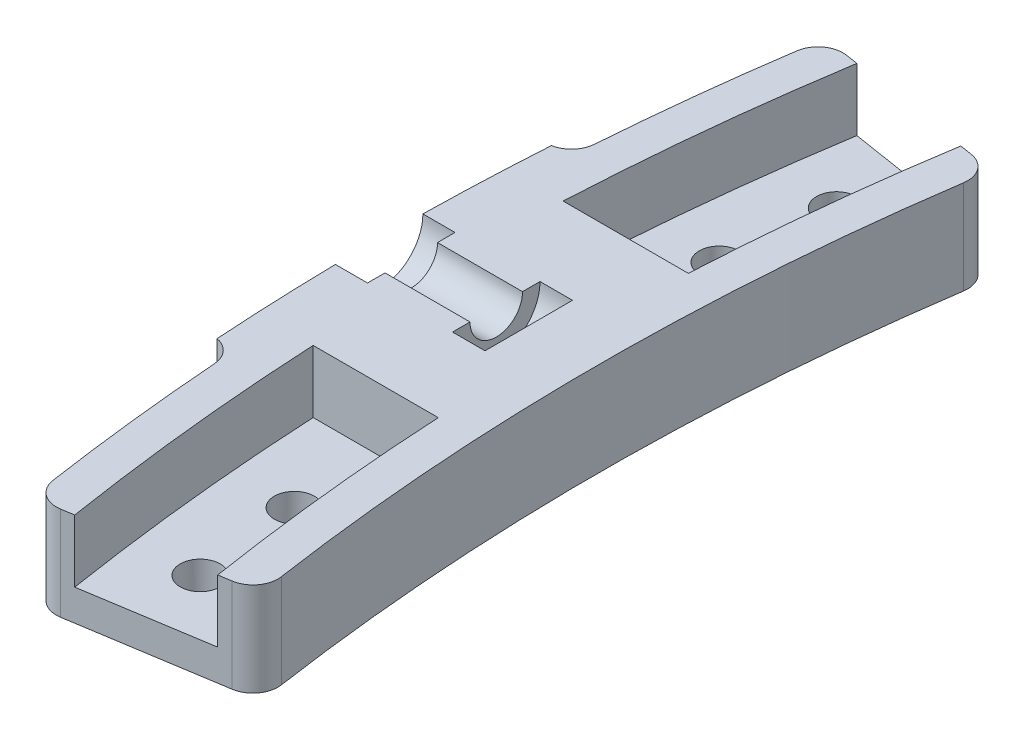
SolidWorks part; units mm, degrees
ref_plane "Front Plane" through (0, 0, 0) normal (0, 0, 1) x (1, 0, 0)
ref_plane "Top Plane" through (0, 0, 0) normal (0, 1, 0) x (1, 0, 0)
ref_plane "Right Plane" through (0, 0, 0) normal (1, 0, 0) x (0, 0, -1)
sketch "Sketch1" plane through (0, 0, 0) normal (0, 1, 0) x (1, 0, 0)
  line L0 (0, 0) -> (-197.5377, -31.2869) construction
  line L1 (0, 0) -> (-197.5377, 31.2869) construction
  line L2 (0, 0) -> (-195, 0) construction
  line L3 (-197.5377, 31.2869) -> (-187.6608, 29.7225)
  line L4 (-187.6608, -29.7225) -> (-197.5377, -31.2869)
  line L5 (0, 0) -> (-200.5007, -31.7562) construction
  line L6 (0, 0) -> (-200.5007, 31.7562) construction
  line L7 (-200.5007, 31.7562) -> (-184.6977, 29.2532)
  line L8 (-200.5007, -31.7562) -> (-184.6977, -29.2532)
  arc A0 (-197.5377, 31.2869) -> (-197.5377, -31.2869) centre (0, 0) ccw
  arc A1 (-187.6608, 29.7225) -> (-187.6608, -29.7225) centre (0, 0) ccw
  arc A2 (-192.5992, -30.5047) -> (-192.5992, 30.5047) centre (0, 0) cw construction
  arc A4 (-184.6977, 29.2532) -> (-184.6977, -29.2532) centre (0, 0) ccw
  arc A5 (-200.5007, 31.7562) -> (-200.5007, -31.7562) centre (0, 0) ccw
  dimension "D1" = 200
  dimension "D2" = 190
  dimension "D3" = 5
  dimension "D5" = 187
  dimension "D6" = 203
  dimension "D4" = 18
extrude "Boss-Extrude1" add sketch "Sketch1" along normal blind 7.5 contours A1 L3 A0 L4 | L7 A5 L8 A0 | A4 L7 A1 L8 region at (-200.6761, 0, 0) region at (-194.2416, 0, 0) region at (-187.7297, 0, 0)
ref_plane "Plane1" through (-195, 0, 0) normal (1, 0, 0) x (0, 0, -1)
sketch "Sketch19" plane through (0, 0, 0) normal (0, 1, 0) x (1, 0, 0)
  line L0 (0, 0) -> (-204.0621, 13.3749) construction
  line L1 (0, 0) -> (-204.0621, -13.3749) construction
  line L4 (0, 0) -> (-204.5, 0) construction
  line L5 (-204.0621, 13.3749) -> (-202.5654, 13.2768)
  line L6 (-204.0621, -13.3749) -> (-202.5654, -13.2768)
  arc A0 (-204.0621, 13.3749) -> (-204.0621, -13.3749) centre (0, 0) ccw
  arc A1 (-200.5007, 31.7562) -> (-200.5007, -31.7562) centre (0, 0) ccw construction
  arc A2 (-202.5654, 13.2768) -> (-202.5654, -13.2768) centre (0, 0) ccw
  dimension "D1" = 204.5
  dimension "D2" = 3.75
extrude "Boss-Extrude2" add sketch "Sketch19" along normal blind 7.5
sketch "Sketch15" plane through (0, 7.5, 0) normal (0, 1, 0) x (1, 0, 0)
  line L0 (-187.6608, -29.7225) -> (-197.5377, -31.2869) construction
  line L1 (-185, 10) -> (-205, 10)
  line L2 (-185, 10) -> (-185, -10)
  line L3 (-185, -10) -> (-205, -10)
  line L4 (-205, 10) -> (-205, -10)
  line L5 (-185, 10) -> (-205, -10) construction
  line L6 (-185, -10) -> (-205, 10) construction
  line L7 (-197.5377, 31.2869) -> (-187.6608, 29.7225) construction
  line L8 (-187.6608, -29.7225) -> (-197.5377, -31.2869)
  line L9 (-197.5377, 31.2869) -> (-187.6608, 29.7225)
  arc A2 (-187.6608, 29.7225) -> (-187.6608, -29.7225) centre (0, 0) ccw construction
  arc A3 (-197.5377, 31.2869) -> (-197.5377, -31.2869) centre (0, 0) ccw construction
  arc A4 (-187.6608, 29.7225) -> (-187.6608, -29.7225) centre (0, 0) ccw
  arc A5 (-197.5377, 31.2869) -> (-197.5377, -31.2869) centre (0, 0) ccw
  point P0 (-195, 0)
  line M5 (-200.5007, -31.7562) -> (-184.6977, -29.2532)
  line M7 (-184.6977, 29.2532) -> (-200.5007, 31.7562)
  dimension "D1" = 20
  dimension "D2" = 20
extrude "Cut-Extrude1" cut sketch "Sketch15" against normal blind 5 contours A5 L1 A4 M7 | L3 A5 A4 M5 region at (-193.9153, 7.5, -20.2762) region at (-193.9153, 7.5, 20.2762)
ref_plane "Plane2" through (-195, 0, 0) normal (-1, 0, 0) x (0, 0, 1)
sketch "Sketch12" plane through (0, 0, 0) normal (0, 1, 0) x (1, 0, 0)
  line L0 (0, 0) -> (-194.258, -16.9954) construction
  line L1 (0, 0) -> (-193.3317, -25.4526) construction
  line L2 (0, 0) -> (-195, 0) construction
  line L3 (0, 0) -> (-195, 0) construction
  line L4 (0, 0) -> (-194.258, 16.9954) construction
  line L5 (0, 0) -> (-193.3317, 25.4526) construction
  arc A0 (-192.5992, 30.5047) -> (-192.5992, -30.5047) centre (0, 0) ccw construction
  dimension "D1" = 10
  dimension "D2" = 15
hole_wizard "Ø3.2 (3.2) Diameter Hole1" positions "Sketch18" profile "Sketch17" hole size "Ø3.2" standard "ISO" end condition through all
sketch "Sketch18" plane through (0, 0, 0) normal (0, -1, 0) x (-1, 0, 0)
  point P0 (193.3317, -25.4526)
  point P3 (194.258, -16.9954)
  point P6 (194.258, 16.9954)
  point P9 (193.3317, 25.4526)
sketch "Sketch17" plane through (-193.3317, 0, 25.4526) normal (1, 0, 0) x (0, 0, -1)
  line L0 (0, 0) -> (0, 7.5)
  line L1 (0, 7.5) -> (1.6, 7.5)
  line L2 (1.6, 7.5) -> (1.6, 0)
  line L5 (1.6, 0) -> (0, 0)
  line L11 (0, -6.35) -> (0, 107.95) construction
  dimension "Thru Hole Dia." = 3.2
  dimension "Thru Hole Depth" = 7.5
sketch "Sketch20" plane through (0, 0, 0) normal (0, 1, 0) x (1, 0, 0)
  line L0 (-205, 0) -> (-192.5, 0) construction
  line L1 (0, 0) -> (-205, 0) construction
  arc A2 (-204.0621, 13.3749) -> (-204.0621, -13.3749) centre (0, 0) ccw construction
  point P3 (-204.5, 0)
  dimension "D1" = 205
  dimension "D2" = 12.5
ref_plane "Plane3" through (-192.5, 0, 0) normal (1, 0, 0) x (0, 0, -1)
sketch "Sketch21" plane through (-192.5, 0, 0) normal (1, 0, 0) x (0, 0, -1)
  line L0 (29.2532, 7.5) -> (-29.2532, 7.5) construction
  circle A0 centre (0, 7.5) radius 3.5
  dimension "D1" = 7
extrude "Cut-Extrude2" cut sketch "Sketch21" against normal blind 2.6
sketch "Sketch22" plane through (-195.1, 0, 0) normal (1, 0, 0) x (0, 0, -1)
  line L0 (29.2532, 7.5) -> (-29.2532, 7.5) construction
  circle A0 centre (0, 7.5) radius 2.1
  dimension "D1" = 4.2
ref_plane "Plane4" through (-204.5, 0, 0) normal (1, 0, 0) x (0, 0, -1)
sketch "Sketch23" plane through (-204.5, 0, 0) normal (1, 0, 0) x (0, 0, -1)
  circle A0 centre (0, 7.5) radius 3.5
  dimension "D1" = 7
extrude "Cut-Extrude3" cut sketch "Sketch23" along normal blind 2.6
extrude "Cut-Extrude4" cut sketch "Sketch22" against normal through all contours A0
fillet "Fillet1" radius 2 4 edges at (-200.5007, 3.75, -31.7562) (-184.6977, 3.75, -29.2532) (-184.6977, 3.75, 29.2532) (-200.5007, 3.75, 31.7562)
fillet "Fillet2" radius 2 2 edges at (-202.5654, 3.75, -13.2768) (-202.5654, 3.75, 13.2768)
